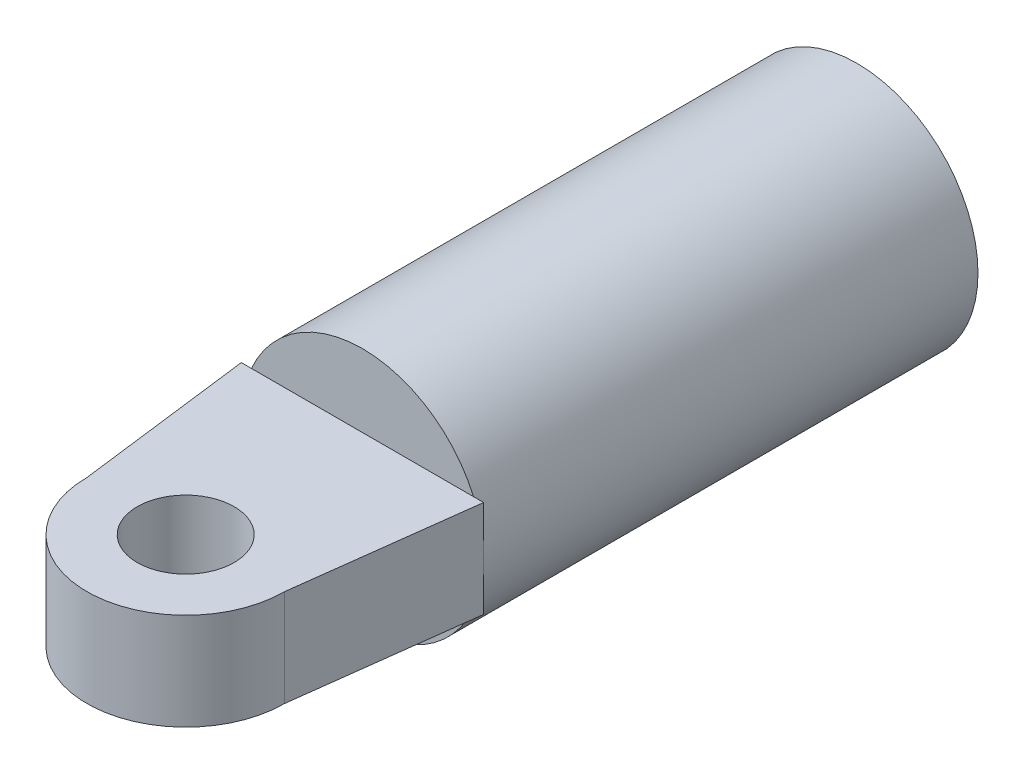
SolidWorks part; units mm, degrees
ref_plane "Спереди" through (0, 0, 0) normal (0, 0, 1) x (1, 0, 0)
ref_plane "Сверху" through (0, 0, 0) normal (0, 1, 0) x (1, 0, 0)
ref_plane "Справа" through (0, 0, 0) normal (1, 0, 0) x (0, 0, -1)
sketch "Эскиз1" plane through (0, 0, 0) normal (0, 0, 1) x (1, 0, 0)
  circle A0 centre (0, 0) radius 12.5
  dimension "D1" = 25
extrude "Бобышка-Вытянуть1" add sketch "Эскиз1" along normal blind 51
sketch "Эскиз2" plane through (0, 0, 0) normal (0, 1, 0) x (0, 0, -1)
  line L0 (-69.2354, 10.1942) -> (-51, 12.5)
  line L1 (-51, 12.5) -> (-51, -12.5)
  line L2 (-51, -12.5) -> (-69.2354, -10.1942)
  circle A0 centre (-69.2354, 0) radius 4.9995
  arc A1 (-69.2354, 10.1942) -> (-69.2354, -10.1942) centre (-69.2354, 0) ccw
  dimension "D1" = 9.999
extrude "Бобышка-Вытянуть2" add sketch "Эскиз2" along normal blind 5 and the other way blind 5
